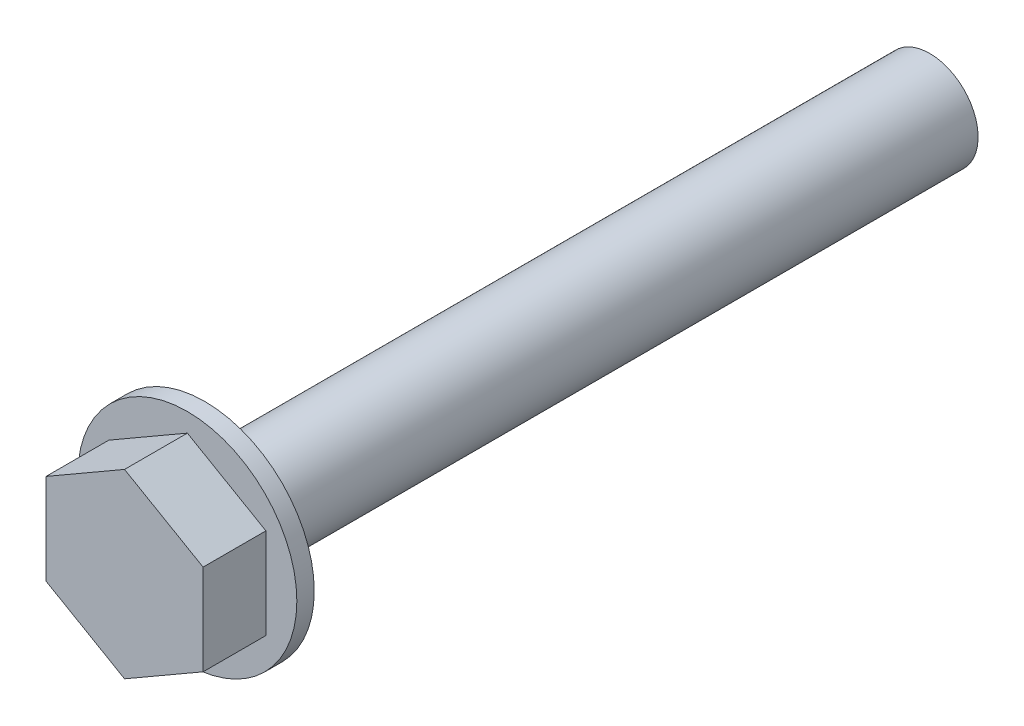
SolidWorks part; units mm, degrees
material "AISI Type 316L stainless steel"
ref_plane "Front Plane" through (0, 0, 0) normal (0, 0, 1) x (1, 0, 0)
ref_plane "Top Plane" through (0, 0, 0) normal (0, 1, 0) x (1, 0, 0)
ref_plane "Right Plane" through (0, 0, 0) normal (1, 0, 0) x (0, 0, -1)
sketch "Extrude sketch 1" plane through (0, 0, 0) normal (0, 0, 1) x (1, 0, 0)
  circle A0 centre (0, 0) radius 9.06
  dimension "D1" = 18.12
extrude "Extrude 1" add sketch "Extrude sketch 1" along normal blind 1.44 separate body
sketch "Extrude sketch 2" plane through (0, 0, 0) normal (0, 0, 1) x (1, 0, 0)
  line L0 (6.5, 3.7528) -> (0, 7.5056)
  line L1 (0, 7.5056) -> (-6.5, 3.7528)
  line L2 (-6.5, 3.7528) -> (-6.5, -3.7528)
  line L3 (-6.5, -3.7528) -> (0, -7.5056)
  line L4 (0, -7.5056) -> (6.5, -3.7528)
  line L5 (6.5, -3.7528) -> (6.5, 3.7528)
  dimension "D1" = 6.5
  dimension "D2" = 3.7528
extrude "Extrude 2" add sketch "Extrude sketch 2" along normal blind 5.2 from offset 1.44 separate body
sketch "Extrude sketch 3" plane through (0, 0, 0) normal (0, 0, 1) x (1, 0, 0)
  circle A0 centre (0, 0) radius 4
  dimension "D1" = 8
extrude "Extrude 3" add sketch "Extrude sketch 3" along normal blind 60.01 from offset 60 separate body offset against normal yes
combine bodies "Combine (weld / assembly of features)" operation type add bodies to combine 102 101 103
